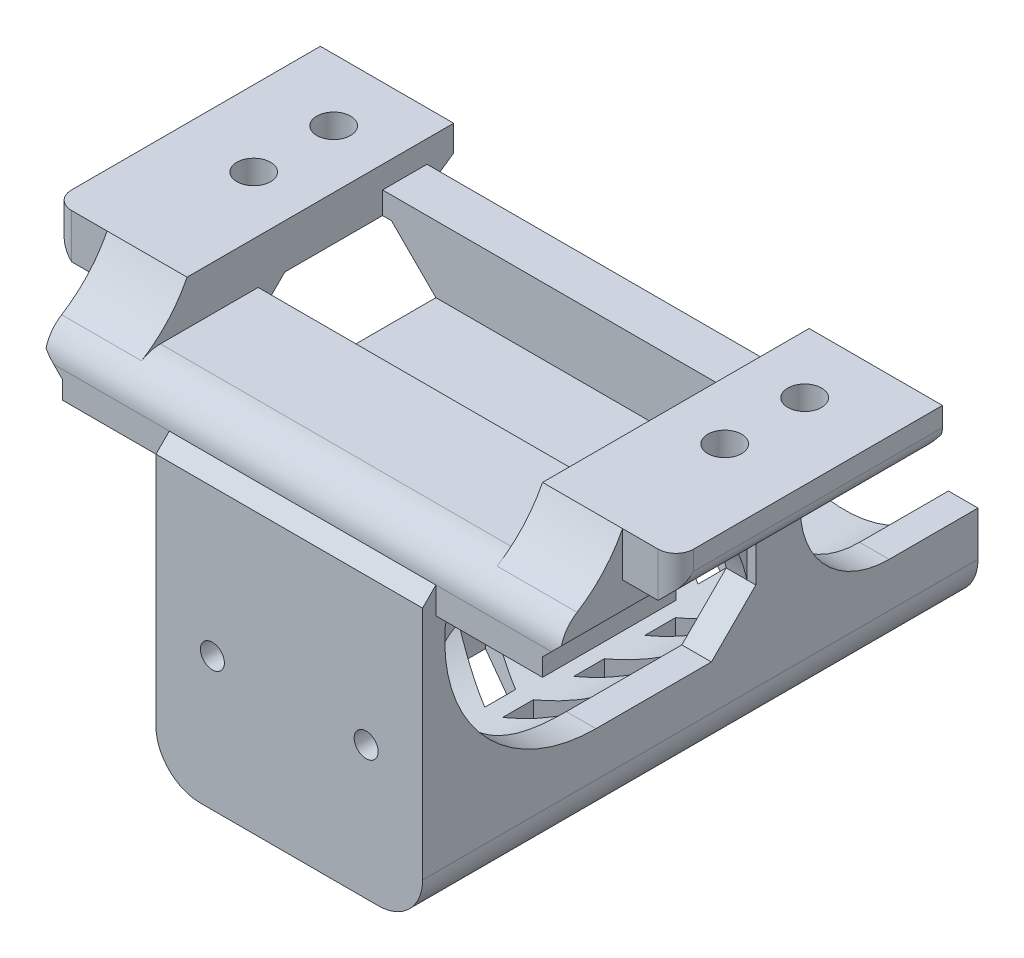
SolidWorks part; units mm, degrees
ref_plane "Front Plane" through (0, 0, 0) normal (0, 0, 1) x (1, 0, 0)
ref_plane "Top Plane" through (0, 0, 0) normal (0, 1, 0) x (1, 0, 0)
ref_plane "Right Plane" through (0, 0, 0) normal (1, 0, 0) x (0, 0, -1)
sketch "Sketch1" plane through (0, 0, 0) normal (0, 1, 0) x (1, 0, 0)
  line L1 (-20, -15) -> (20, -15)
  line L2 (-20, -15) -> (-20, 15)
  line L3 (-20, 15) -> (20, 15)
  line L4 (20, -15) -> (20, 15)
  line L5 (-20, -15) -> (20, 15) construction
  line L6 (-20, 15) -> (20, -15) construction
  line L7 (20, 15) -> (35, 15)
  line L8 (20, 15) -> (20, -15)
  line L9 (20, -15) -> (35, -15)
  line L10 (35, 15) -> (35, -15)
  line L11 (-20, 15) -> (-35, 15)
  line L12 (-20, 15) -> (-20, -15)
  line L13 (-20, -15) -> (-35, -15)
  line L14 (-35, 15) -> (-35, -15)
  point P0 (0, 0)
  dimension "D1" = 40
  dimension "D2" = 30
  dimension "D3" = 15
  dimension "D4" = 15
extrude "Boss-Extrude1" add sketch "Sketch1" against normal blind 5 contours L10 L7 L4 L9 | L11 L14 L13 L2 region at (-27.5, 0, 0) region at (27.5, 0, 0)
sketch "Sketch2" plane through (0, -5, 0) normal (0, -1, 0) x (1, 0, 0)
  line L0 (-29, 7) -> (29, 7)
  line L6 (-29, 7) -> (-29, 22)
  line L7 (-29, 22) -> (29, 22)
  line L8 (29, 7) -> (29, 22)
  line L10 (20, 15) -> (35, 15) construction
  line L11 (-35, -15) -> (-35, 15) construction
  line L12 (35, -15) -> (35, 15) construction
  line L15 (29, -2.2959) -> (29, 22)
  line L16 (29, 22) -> (9.2581, 22)
  line L18 (-29, 22) -> (-7.63, 22)
  line L19 (-29, 22) -> (-29, -0.8097)
  line M4 (-20, -15) -> (-20, 15)
  line M5 (-20, 15) -> (-35, 15)
  dimension "D1" = 8
  dimension "D2" = 15
  dimension "D3" = 6
  dimension "D4" = 6
extrude "Boss-Extrude2" add sketch "Sketch2" along normal blind 5 contours L0 L8 L7 L6 M5 M4 | L6 L0 M4 M5 region at (-24.5, -5, 11) region at (2.2105, -5, 14.8158)
chamfer "Chamfer1" distance 3 angle 45 2 edges at (24.5, -5, 7) (-24.5, -5, 7)
chamfer "Chamfer2" distance 2 angle 45 4 edges at (29, -10, 14.5) (-29, -10, 14.5) (35, -5, 0) (-35, -5, 0)
chamfer "Chamfer4" distance 3 angle 35 2 edges at (26.5, -5, -15) (-26.5, -5, -15) first distance on face at (27.3333, -5, 1.3333) first distance on face at (-27.3333, -5, 1.3333)
fillet "Fillet1" radius 4 1 edges at (0, -5, 22)
fillet "Fillet2" radius 14 2 edges at (24.5, -5, 15) (-24.5, -5, 15)
fillet "Fillet4" radius 2 4 edges at (35, -3, 0.0719) (-35, -3, 0.0719) (35, -1.5, 15) (-35, -1.5, 15)
sketch "Sketch3" plane through (0, -10, 0) normal (0, -1, 0) x (1, 0, 0)
  line L1 (-27, 7) -> (27, 7)
  line L2 (-27, 7) -> (-27, 22)
  line L3 (-27, 22) -> (27, 22)
  line L4 (27, 7) -> (27, 22)
extrude "Boss-Extrude3" add sketch "Sketch3" along normal blind 2
sketch "Sketch4" plane through (0, 0, 22) normal (0, 0, 1) x (1, 0, 0)
  line L0 (0, 6.1522) -> (0, -54.3246) construction
  line L1 (30.4892, -12) -> (-35.9892, -12) construction
  line L3 (-15, -12) -> (15, -12)
  line L4 (-15, -12) -> (-15, -42)
  line L5 (-15, -42) -> (15, -42)
  line L6 (15, -12) -> (15, -42)
  dimension "D1" = 30
  dimension "D2" = 30
  dimension "D3" = 15
extrude "Boss-Extrude4" add sketch "Sketch4" against normal blind 2.5 from offset 1.5
fillet "Fillet5" radius 2 1 edges at (0, -12, 21)
chamfer "Chamfer6" distance 3 angle 45 1 edges at (0, -12, 22)
sketch "Sketch5" plane through (0, 0, 23.5) normal (0, 0, 1) x (1, 0, 0)
  line L0 (0, 0) -> (0, -48.8189) construction
  line L1 (27, -12) -> (15, -12) construction
  circle A0 centre (0, -27) radius 8.65 construction
  circle A1 centre (8.65, -27) radius 1.35
  circle A2 centre (-8.65, -27) radius 1.35
  dimension "D1" = 17.3
  dimension "D3" = 2.7
  dimension "D4" = 2.7
  dimension "D2" = 15
extrude "Cut-Extrude1" cut sketch "Sketch5" against normal blind 12.7
fillet "Fillet6" radius 5 2 edges at (15, -42, 22.25) (-15, -42, 22.25)
sketch "Sketch7" plane through (0, 0, 21) normal (0, 0, -1) x (-1, 0, 0)
  line L0 (15, -32) -> (11.6743, -32)
  line L1 (-11.6743, -32) -> (-22.4769, -32)
  line L4 (-15, -14) -> (-15, -37)
  line L5 (-10, -42) -> (10, -42)
  line L6 (15, -37) -> (15, -14)
  line L7 (15, -14) -> (-15, -14)
  line L8 (-15, -14) -> (-15, -37)
  line L9 (-10, -42) -> (10, -42)
  line L10 (15, -37) -> (15, -14)
  line L11 (15, -14) -> (-15, -14)
  circle A1 centre (0, -27) radius 12.7
  arc A2 (-15, -37) -> (-10, -42) centre (-10, -37) ccw
  arc A3 (10, -42) -> (15, -37) centre (10, -37) ccw
  arc A4 (-15, -37) -> (-10, -42) centre (-10, -37) ccw
  arc A5 (10, -42) -> (15, -37) centre (10, -37) ccw
  line M10 (-15, -14) -> (-15, -37)
  arc M11 (-15, -37) -> (-10, -42) centre (-10, -37) ccw
  line M12 (-10, -42) -> (10, -42)
  arc M13 (10, -42) -> (15, -37) centre (10, -37) ccw
  line M14 (15, -37) -> (15, -14)
  dimension "D3" = 25.4
  dimension "D2" = 10
  dimension "D1" = 0
extrude "Boss-Extrude5" add sketch "Sketch7" along normal blind 60 contours A1 L1 L0 M10 M11 M12 M13 M14 region at (-14.6838, -34.5, 21)
fillet "Fillet7" radius 17 2 edges at (-13.3372, -32, 21) (13.3372, -32, 21)
sketch "Sketch8" plane through (0, -32, 0) normal (0, 1, 0) x (1, 0, 0)
  line L0 (-11.6743, 39) -> (-11.6743, -4) construction
  line L1 (-11.6743, 14) -> (-15, 14)
  line L2 (-11.6743, 14) -> (-11.6743, 19)
  line L3 (-11.6743, 19) -> (-15, 19)
  line L4 (-15, 14) -> (-15, 19)
  line L5 (-15, 39) -> (-15, -4) construction
  line L6 (15, -23.5) -> (15, 39) construction
  line L7 (15, 14) -> (11.6743, 14)
  line L8 (15, 14) -> (15, 19)
  line L9 (15, 19) -> (11.6743, 19)
  line L10 (11.6743, 14) -> (11.6743, 19)
  line L11 (11.6743, 39) -> (11.6743, -4) construction
  line L12 (-15, 39) -> (-11.6743, 39) construction
  line L13 (11.6743, 39) -> (15, 39) construction
  dimension "D1" = 20
  dimension "D2" = 5
  dimension "D3" = 20
  dimension "D4" = 5
extrude "Boss-Extrude6" add sketch "Sketch8" along normal blind 18
fillet "Fillet8" radius 10 2 edges at (13.3372, -32, -19) (-13.3372, -32, -19)
chamfer "Chamfer8" distance 5 angle 45 2 edges at (-13.3372, -32, -14) (13.3372, -32, -14)
sketch "Sketch9" plane through (0, 0, -14) normal (0, 0, 1) x (1, 0, 0)
  line L0 (-15, -14) -> (-15, -27) construction
  line L1 (-14, -15) -> (-9, -15)
  line L2 (-14, -15) -> (-14, -10)
  line L3 (-14, -10) -> (14, -10)
  line L4 (14, -15) -> (14, -10)
  line L5 (15, -14) -> (15, -27) construction
  line L6 (-15, -14) -> (-11.6743, -14) construction
  line L7 (9, -15) -> (14, -15)
  circle A0 centre (0, -27) radius 15
  line M7 (-11.6743, -27) -> (-11.6743, -14)
  line M8 (-11.6743, -14) -> (-15, -14)
  dimension "D5" = 30
  dimension "D1" = 1
  dimension "D2" = 1
  dimension "D3" = 1
  dimension "D4" = 5
extrude "Boss-Extrude8" add sketch "Sketch9" along normal up to next contours A0 L7 L4 L3 L2 L1 M8 M7 | L2 L1 M7 M8 region at (-12.8372, -14.5, -14) region at (0.2959, -11.9838, -14)
fillet "Fillet9" radius 5 2 edges at (12.8372, -14, -14) (-12.8372, -14, -14)
fillet "Fillet10" radius 15 2 edges at (12.8372, -15, -14) (-12.8372, -15, -14)
sketch "Sketch10" plane through (0, -10, 0) normal (0, 1, 0) x (1, 0, 0)
  line L0 (14, -7) -> (14, 14) construction
  line L1 (-14, 14) -> (14, 14)
  line L2 (-14, 14) -> (-14, 7)
  line L3 (-14, 7) -> (14, 7)
  line L4 (14, 14) -> (14, 7)
  dimension "D1" = 7
extrude "Boss-Extrude9" add sketch "Sketch10" along normal blind 5
sketch "Sketch11" plane through (0, -5, 0) normal (0, 1, 0) x (1, 0, 0)
  line L0 (-20, 15) -> (-35, 15) construction
  line L1 (-25, 7) -> (25, 7)
  line L2 (-25, 7) -> (-25, 12)
  line L3 (-25, 12) -> (25, 12)
  line L4 (25, 7) -> (25, 12)
  line L6 (-20, -15) -> (-20, 15) construction
  line L7 (20, -15) -> (20, 15) construction
  dimension "D1" = 3
  dimension "D2" = 5
  dimension "D3" = 5
  dimension "D4" = 5
extrude "Boss-Extrude10" add sketch "Sketch11" along normal blind 2.5
chamfer "Chamfer9" distance 5 angle 45 2 edges at (14, -5, -9.5) (-14, -5, -9.5)
sketch "Sketch12" plane through (0, 0, 0) normal (0, 1, 0) x (1, 0, 0)
  line L0 (26.5, -24.327) -> (26.5, 25.0315) construction
  line L1 (33, 12) -> (33, -15) construction
  line L2 (20, -4) -> (20, 7) construction
  line L3 (-26.5, -35.1265) -> (-26.5, 37.3487) construction
  line L4 (-33, -15) -> (-33, 12) construction
  line L5 (-20, -4) -> (-20, 7) construction
  line L6 (-20, 15) -> (-34.8629, 15) construction
  line L7 (34.8629, 15) -> (20, 15) construction
  circle A0 centre (-26.5, 8) radius 1.9
  circle A1 centre (-26.5, -1) radius 1.9
  circle A2 centre (26.5, -1) radius 1.9
  circle A3 centre (26.5, 8) radius 1.9
  dimension "D1" = 3.8
  dimension "D2" = 3.8
  dimension "D3" = 3.8
  dimension "D4" = 3.8
  dimension "D5" = 7
  dimension "D6" = 9
  dimension "D7" = 7
  dimension "D8" = 9
extrude "Cut-Extrude2" cut sketch "Sketch12" against normal mid plane 20
fillet "Fillet11" radius 3 2 edges at (11.5, -15, 21) (-11.5, -15, 21)
sketch "Sketch13" plane through (0, -42, 0) normal (0, -1, 0) x (1, 0, 0)
  line L0 (0, -41.5515) -> (0, 29.253) construction
  line L1 (1, 16.5) -> (9, 11.8812)
  line L2 (1, 16.5) -> (1, 13.0359)
  line L3 (9, 11.8812) -> (9, 8.4171)
  line L4 (1, 13.0359) -> (9, 8.4171)
  line L5 (10, -39) -> (10, 23.5) construction
  line L6 (-10, 23.5) -> (10, 23.5) construction
  line L7 (1, 8.5) -> (9, 3.8812)
  line L8 (1, 8.5) -> (1, 5.0359)
  line L9 (1, 5.0359) -> (9, 0.4171)
  line L10 (9, 3.8812) -> (9, 0.4171)
  line L11 (1, 0.5) -> (9, -4.1188)
  line L12 (1, 0.5) -> (1, -2.9641)
  line L13 (1, -2.9641) -> (9, -7.5829)
  line L14 (9, -4.1188) -> (9, -7.5829)
  line L15 (1, -7.5) -> (9, -12.1188)
  line L16 (1, -7.5) -> (1, -10.9641)
  line L17 (1, -10.9641) -> (9, -15.5829)
  line L18 (9, -12.1188) -> (9, -15.5829)
  line L19 (1, -15.5) -> (9, -20.1188)
  line L20 (1, -15.5) -> (1, -18.9641)
  line L21 (1, -18.9641) -> (9, -23.5829)
  line L22 (9, -20.1188) -> (9, -23.5829)
  line L23 (1, -23.5) -> (9, -28.1188)
  line L24 (1, -23.5) -> (1, -26.9641)
  line L25 (1, -26.9641) -> (9, -31.5829)
  line L26 (9, -28.1188) -> (9, -31.5829)
  dimension "D1" = 1
  dimension "D2" = 1
  dimension "D3" = 3
  dimension "D4" = 7
  dimension "D5" = 60
  dimension "D6" = 6
extrude "Cut-Extrude3" cut sketch "Sketch13" against normal mid plane 20
mirror "Mirror1" about plane through (0, 0, 0) normal (1, 0, 0) of "Cut-Extrude3"
chamfer "Chamfer10" distance 2 angle 45 1 edges at (0, -5, -12)
